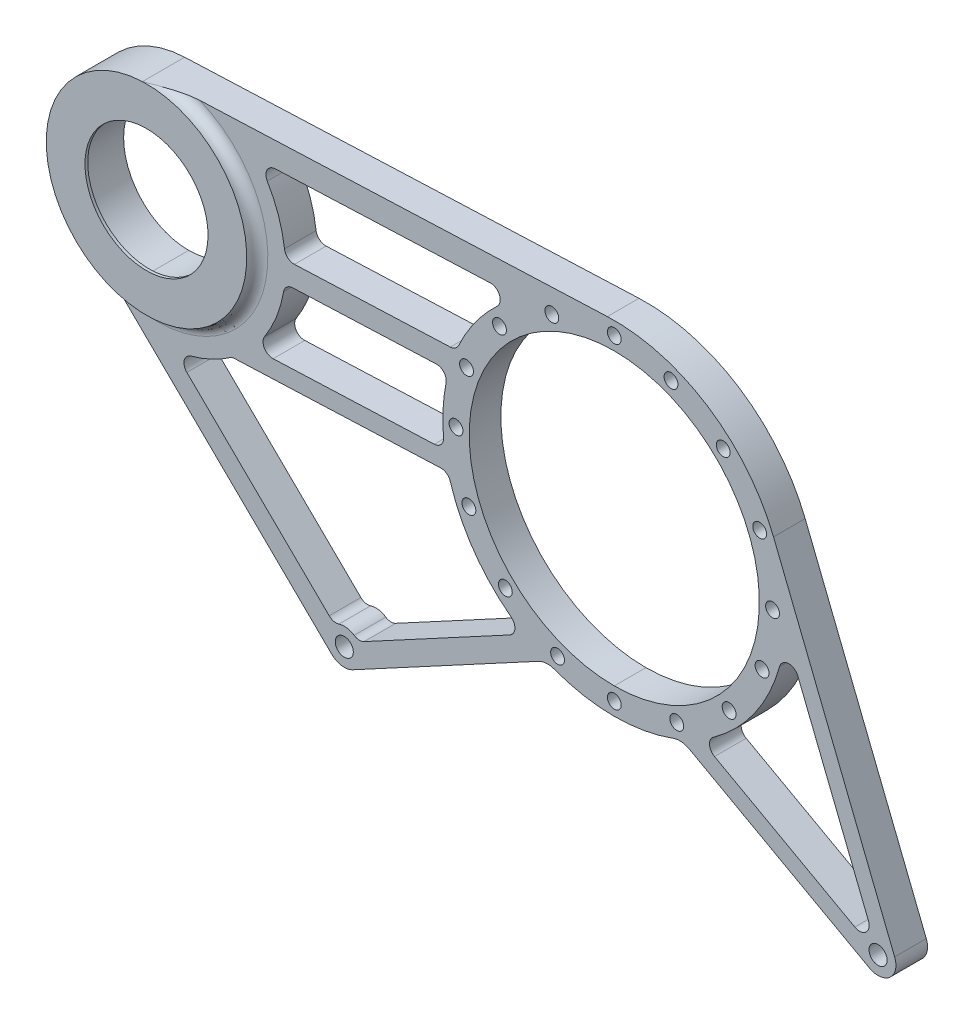
SolidWorks part; units mm, degrees
material "6061-T6 (SS)"
ref_plane "Front Plane" through (0, 0, 0) normal (0, 0, 1) x (1, 0, 0)
ref_plane "Top Plane" through (0, 0, 0) normal (0, 1, 0) x (1, 0, 0)
ref_plane "Right Plane" through (0, 0, 0) normal (1, 0, 0) x (0, 0, -1)
sketch "Sketch1" plane through (0, 0, 0) normal (0, 0, 1) x (1, 0, 0)
  line L0 (-114.3, 95.25) -> (-114.3, 107.95) construction
  line L1 (-280.8642, 163.1704) -> (-116.8043, 169.8118)
  line L2 (-304.7421, 101.1501) -> (-216.3071, 14.4521)
  line L3 (-13.0706, 21.4387) -> (-56.8054, 130.918)
  line L4 (-208.742, 13.3833) -> (-141.7118, 49.5504)
  line L5 (-22.1639, 13.4141) -> (-87.2342, 49.3665)
  circle A0 centre (-279.4, 127) radius 23.5
  circle A1 centre (-114.3, 95.25) radius 36 construction
  circle A2 centre (0, 0) radius 12.7 construction
  circle A3 centre (-228.6, 0) radius 12.7 construction
  circle A4 centre (-114.3, 107.95) radius 52.3875
  circle A5 centre (-19.05, 19.05) radius 3.2639
  circle A6 centre (-211.7995, 19.05) radius 3.2639
  circle A7 centre (-279.4, 127) radius 36.2
  arc A8 (-135.9521, 49.947) -> (-93.0137, 49.8118) centre (-114.3, 107.95) ccw
  arc A9 (-216.3071, 14.4521) -> (-208.742, 13.3833) centre (-211.7995, 19.05) ccw
  arc A10 (-22.1639, 13.4141) -> (-13.0706, 21.4387) centre (-19.05, 19.05) ccw
  arc A11 (-56.8054, 130.918) -> (-116.8043, 169.8118) centre (-114.3, 107.95) ccw
  arc A12 (-135.9521, 49.947) -> (-141.7118, 49.5504) centre (-138.3949, 43.4031) ccw
  arc A13 (-87.2342, 49.3665) -> (-93.0137, 49.8118) centre (-90.6122, 43.2526) ccw
  dimension "D5" = 72
  dimension "D6" = 47
  dimension "D7" = 25.4
  dimension "D8" = 25.4
  dimension "D11" = 104.775
  dimension "D14" = 6.5278
  dimension "D15" = 6.5278
  dimension "D16" = 25.4
  dimension "D17" = 12.7
  dimension "D18" = 123.825
  dimension "D19" = 3.175
  dimension "D20" = 6.985
  dimension "D21" = 6.985
  dimension "D1" = 114.3
  dimension "D2" = 95.25
  dimension "D3" = 279.4
  dimension "D4" = 127
  dimension "D9" = 228.6
  dimension "D10" = 12.7
  dimension "D12" = 19.05
  dimension "D13" = 19.05
extrude "Boss-Extrude1" add sketch "Sketch1" along normal blind 11.43 contours A13 L5 A10 L3 A11 L1 A7 L2 A9 L4 A12 A8 A6 A5 A4 | A7 A0 region at (-168.693, 91.0379, 0) region at (-255.035, 152.3713, 0)
sketch "Sketch2" plane through (0, 0, 11.43) normal (0, 0, 1) x (1, 0, 0)
  circle A0 centre (-279.4, 127) radius 36.2
  circle A1 centre (-279.4, 127) radius 23.5
extrude "Boss-Extrude2" add sketch "Sketch2" along normal blind 3.81
fillet "Fillet1" radius 3.81 1 edges at (-245.6173, 113.9936, 11.43)
sketch "Sketch3" plane through (0, 0, 11.43) normal (0, 0, 1) x (1, 0, 0)
  line L0 (-114.3, 107.95) -> (-114.3, 165.1) construction
  line L1 (-114.3, 107.95) -> (-57.15, 107.95) construction
  line L2 (-114.3, 107.95) -> (-114.3, 50.8) construction
  line L3 (-114.3, 107.95) -> (-171.45, 107.95) construction
  line L4 (-114.3, 107.95) -> (-93.8193, 161.3041) construction
  line L5 (-114.3, 107.95) -> (-74.9605, 149.4051) construction
  line L6 (-114.3, 107.95) -> (-61.7911, 130.5096) construction
  line L7 (-114.3, 107.95) -> (-60.9459, 87.4693) construction
  line L8 (-114.3, 107.95) -> (-72.8449, 68.6105) construction
  line L9 (-114.3, 107.95) -> (-91.7404, 55.4411) construction
  line L10 (-114.3, 107.95) -> (-134.7807, 54.5959) construction
  line L11 (-114.3, 107.95) -> (-153.6395, 66.4949) construction
  line L12 (-114.3, 107.95) -> (-166.8089, 85.3904) construction
  line L13 (-114.3, 107.95) -> (-167.6541, 128.4307) construction
  line L14 (-114.3, 107.95) -> (-155.7551, 147.2895) construction
  line L15 (-114.3, 107.95) -> (-136.8596, 160.4589) construction
  circle A0 centre (-114.3, 107.95) radius 57.15 construction
  circle A1 centre (-114.3, 165.1) radius 2.5
  circle A2 centre (-57.15, 107.95) radius 2.5
  circle A3 centre (-114.3, 50.8) radius 2.5
  circle A4 centre (-171.45, 107.95) radius 2.5
  circle A5 centre (-93.8193, 161.3041) radius 2.5
  circle A6 centre (-74.9605, 149.4051) radius 2.5
  circle A7 centre (-61.7911, 130.5096) radius 2.5
  circle A8 centre (-60.9459, 87.4693) radius 2.5
  circle A9 centre (-72.8449, 68.6105) radius 2.5
  circle A10 centre (-91.7404, 55.4411) radius 2.5
  circle A11 centre (-134.7807, 54.5959) radius 2.5
  circle A12 centre (-153.6395, 66.4949) radius 2.5
  circle A13 centre (-166.8089, 85.3904) radius 2.5
  circle A14 centre (-167.6541, 128.4307) radius 2.5
  circle A15 centre (-155.7551, 147.2895) radius 2.5
  circle A16 centre (-136.8596, 160.4589) radius 2.5
  point P14 (-114.3, 107.95)
  point P25 (-114.3, 107.95)
  point P41 (-114.3, 107.95)
  dimension "D1" = 114.3
  dimension "D2" = 5
  dimension "D3" = 4
  dimension "D4" = 21
  dimension "D5" = 43.5
  dimension "D6" = 66.75
  dimension "D7" = 5
  dimension "D8" = 5
  dimension "D9" = 5
extrude "5mm Holes" cut sketch "Sketch3" against normal through all
sketch "Sketch4" plane through (0, 0, 15.24) normal (0, 0, 1) x (1, 0, 0)
  circle A0 centre (-279.4, 127) radius 22.225
  circle A1 centre (-279.4, 127) radius 23.5 construction
  circle A2 centre (-279.4, 127) radius 23.5
  dimension "D1" = 44.45
extrude "Boss-Extrude3" add sketch "Sketch4" against normal blind 1
sketch "Sketch5" plane through (0, 0, 11.43) normal (0, 0, 1) x (1, 0, 0)
  line L0 (-48.0193, 91.8071) -> (-22.5033, 27.9342)
  line L1 (-13.0706, 21.4387) -> (-56.8054, 130.918) construction
  line L2 (-78.1047, 51.5771) -> (-27.4356, 23.5816)
  line L3 (-22.1639, 13.4141) -> (-87.2342, 49.3665) construction
  line L4 (-236.7455, 156.0591) -> (-159.125, 159.2013)
  line L5 (-263.8382, 163.8596) -> (-116.8043, 169.8118) construction
  line L6 (-229.7856, 129.649) -> (-173.517, 131.9269)
  line L7 (-230.4174, 121.9972) -> (-178.6103, 124.0944)
  line L8 (-268.6449, 76.4329) -> (-217.2302, 26.028)
  line L9 (-204.6483, 24.2506) -> (-152.0143, 52.6499)
  line L10 (-292.5742, 89.2212) -> (-216.3071, 14.4521) construction
  line L11 (-208.742, 13.3833) -> (-141.7118, 49.5504) construction
  line L12 (-237.4937, 96.2899) -> (-179.3047, 98.6455)
  line L13 (-251.3498, 89.3738) -> (-177.0086, 92.3833)
  arc A0 (-175.0426, 119.9291) -> (-175.9673, 102.4457) centre (-114.3, 107.95) ccw construction
  circle A1 centre (-211.7995, 19.05) radius 6.4389 construction
  circle A2 centre (-19.05, 19.05) radius 6.4389 construction
  arc A3 (-54.6287, 91.4427) -> (-78.4387, 57.481) centre (-114.3, 107.95) cw
  arc A4 (-48.0193, 91.8071) -> (-54.6287, 91.4427) centre (-51.2626, 90.5115) ccw
  arc A5 (-27.4356, 23.5816) -> (-22.5033, 27.9342) centre (-25.7466, 26.6385) ccw
  arc A6 (-78.1047, 51.5771) -> (-78.4387, 57.481) centre (-76.4157, 54.634) cw
  arc A7 (-233.3928, 132.7086) -> (-253.1835, 88.7646) centre (-279.4, 127) ccw construction
  arc A8 (-292.5742, 89.2212) -> (-263.8382, 163.8596) centre (-279.4, 127) ccw construction
  arc A9 (-213.7352, 25.191) -> (-208.2383, 24.4145) centre (-211.7995, 19.05) cw
  arc A10 (-156.5977, 153.1613) -> (-170.4887, 133.9499) centre (-114.3, 107.95) ccw
  arc A11 (-175.0426, 119.9291) -> (-175.9673, 102.4457) centre (-114.3, 107.95) ccw
  arc A12 (-173.5263, 89.9112) -> (-151.5703, 58.5123) centre (-114.3, 107.95) ccw
  arc A13 (-239.6024, 150.7781) -> (-233.3928, 132.7086) centre (-279.4, 127) cw
  arc A14 (-233.7176, 119.1025) -> (-240.5609, 101.6865) centre (-279.4, 127) cw
  arc A15 (-240.5609, 101.6865) -> (-233.7176, 119.1025) centre (-279.4, 127) ccw construction
  arc A16 (-253.1835, 88.7646) -> (-267.1247, 82.2947) centre (-279.4, 127) cw
  arc A17 (-159.125, 159.2013) -> (-156.5977, 153.1613) centre (-158.9837, 155.7117) cw
  arc A18 (-173.517, 131.9269) -> (-170.4887, 133.9499) centre (-173.6583, 135.4165) ccw
  arc A19 (-229.7856, 129.649) -> (-233.3928, 132.7086) centre (-229.9269, 133.1386) cw
  arc A20 (-236.7455, 156.0591) -> (-239.6024, 150.7781) centre (-236.6043, 152.5695) ccw
  arc A21 (-179.3047, 98.6455) -> (-175.9673, 102.4457) centre (-179.446, 102.1352) ccw
  arc A22 (-178.6103, 124.0944) -> (-175.0426, 119.9291) centre (-178.4691, 120.6048) cw
  arc A23 (-230.4174, 121.9972) -> (-233.7176, 119.1025) centre (-230.2762, 118.5075) ccw
  arc A24 (-237.4937, 96.2899) -> (-240.5609, 101.6865) centre (-237.6349, 99.7796) cw
  arc A25 (-217.2302, 26.028) -> (-213.7352, 25.191) centre (-214.7852, 28.522) ccw
  arc A26 (-204.6483, 24.2506) -> (-208.2383, 24.4145) centre (-206.3067, 27.3242) cw
  arc A27 (-152.0143, 52.6499) -> (-151.5703, 58.5123) centre (-153.6727, 55.7236) ccw
  arc A28 (-177.0086, 92.3833) -> (-173.5263, 89.9112) centre (-176.8673, 88.8936) cw
  arc A29 (-251.3498, 89.3738) -> (-253.1835, 88.7646) centre (-251.2085, 85.8842) ccw
  arc A30 (-268.6449, 76.4329) -> (-267.1247, 82.2947) centre (-266.1999, 78.9268) cw
  arc A31 (-173.5263, 89.9112) -> (-170.4887, 133.9499) centre (-114.3, 107.95) ccw construction
  point P17 (-52.5701, 103.1988)
  point P23 (-83.2204, 54.4036)
  point P51 (-148.3837, 159.6362)
  point P54 (-171.3442, 132.0148)
  point P60 (-243.0732, 155.8029)
  point P63 (-175.5324, 98.7982)
  point P66 (-174.02, 124.2803)
  point P75 (-215.4925, 24.3245)
  point P78 (-206.7898, 23.0951)
  point P81 (-146.981, 55.3657)
  point P84 (-174.2524, 92.4948)
  point P90 (-273.3418, 81.0375)
  dimension "D1" = 123.825
  dimension "D2" = 12.8778
  dimension "D5" = 3.4925
  dimension "D6" = 6.35
  dimension "D14" = 3.4925
  dimension "D3" = 6.35
  dimension "D4" = 6.35
  dimension "D7" = 8.89
  dimension "D8" = 7.62
  dimension "D9" = 7.62
  dimension "D10" = 7.62
  dimension "D11" = 6.35
  dimension "D12" = 25.4
  dimension "D13" = 26.67
extrude "Cut-Extrude2" cut sketch "Sketch5" against normal through all both and the other way through all
ref_axis "Axis2" through (-279.4, 127, 14.24) along (0, 0, -1)
ref_axis "Axis1" through (-114.3, 107.95, 11.43) along (0, 0, -1)
ref_plane "Plane1" through (-114.3, 0, 0) normal (1, 0, 0) x (0, 0, -1)
ref_plane "Plane2" through (-279.4, 0, 0) normal (1, 0, 0) x (0, 0, -1)
ref_plane "Plane3" through (0, 0, 5.715) normal (0, 0, -1) x (-1, 0, 0)
ref_plane "Plane4" through (0, 0, 7.12) normal (0, 0, -1) x (-1, 0, 0)
split line "Split Line1"
split line "Split Line2"
sketch "Sketch6" plane through (0, 0, 5.715) normal (0, 0, -1) x (-1, 0, 0)
  circle A1 centre (114.3, 107.95) radius 52.3875 construction
sketch "Sketch7" plane through (0, 0, 7.12) normal (0, 0, -1) x (-1, 0, 0)
  circle A0 centre (279.4, 127) radius 23.5
